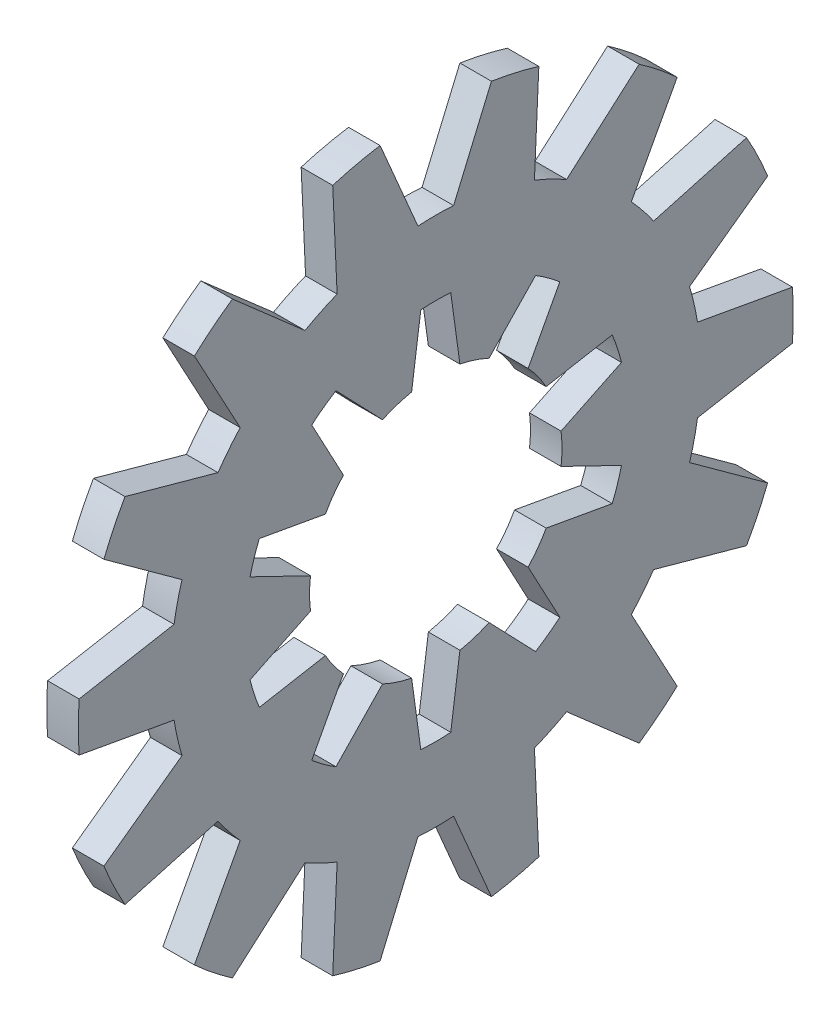
SolidWorks part; units mm, degrees
ref_plane "Plane1" through (0, 0, 0) normal (0, 0, 1) x (1, 0, 0)
ref_plane "Plane2" through (0, 0, 0) normal (0, 1, 0) x (1, 0, 0)
ref_plane "Plane3" through (0, 0, 0) normal (1, 0, 0) x (0, 0, -1)
sketch "SecSke" plane through (0, 0, 0) normal (0, 0, 1) x (1, 0, 0)
  line L0 (-34.925, 0) -> (9.525, 0) construction
  line L1 (0, 3.2512) -> (0, 9.2075)
  line L2 (0, 9.2075) -> (-0.8128, 9.2075)
  line L3 (-0.8128, 9.2075) -> (-0.8128, 3.2512)
  line L4 (-0.8128, 3.2512) -> (0, 3.2512)
  dimension "Thickness" = 0.8128
revolve "Body" add sketch "SecSke" angle 360 about L0
sketch "ExtCutSke" plane through (0, 0, 0) normal (1, 0, 0) x (0, 0, -1)
  line L0 (0, 0) -> (0, 9.6679) construction
  line L1 (-1.6194, 9.5313) -> (-0.4591, 6.8095)
  line L2 (1.6194, 9.5313) -> (0.4591, 6.8095)
  arc A0 (1.6194, 9.5313) -> (-1.6194, 9.5313) centre (0, 0) ccw
  arc A1 (0.4591, 6.8095) -> (-0.4591, 6.8095) centre (0, 0) ccw
extrude "ExtCut" cut sketch "ExtCutSke" against normal through all
pattern_circular "ExtCuts" count 14 every 25.714 about axis through (-34.925, 0, 0) along (1, 0, 0) of "ExtCut"
sketch "IntCutSke" plane through (0, 0, 0) normal (1, 0, 0) x (0, 0, -1)
  line L0 (-0.3859, 4.9038) -> (-0.6453, 3.0205)
  line L1 (0.3859, 4.9038) -> (0.6453, 3.0205)
  line L2 (0, 0) -> (0, 4.919) construction
  arc A0 (0.6453, 3.0205) -> (-0.6453, 3.0205) centre (0, 0) ccw
  arc A1 (0.3859, 4.9038) -> (-0.3859, 4.9038) centre (0, 0) ccw
  dimension "Clr_dia" = 6.1773
  dimension "Clr_ang" = 24.12
  dimension "Cut_ang" = 9
extrude "IntCut" cut sketch "IntCutSke" against normal through all
pattern_circular "IntCuts" count 10 every 36 about axis through (-34.925, 0, 0) along (1, 0, 0) of "IntCut"
equation "' \"Inside_dia@SecSke\" = 16"
equation "' \"Outside_dia@SecSke\" = 35"
equation "' \"Thickness@SecSke\" = 1.4"
equation "' \"Count@ExtCuts\" = 16"
equation "' \"Count@IntCuts\" = 12"
equation "' \"Inside_dia@SecSke\" = 10.5"
equation "' \"Outside_dia@SecSke\" = 26"
equation "' \"Thickness@SecSke\" = 1"
equation "' \"Count@ExtCuts\" = 14"
equation "' \"Count@IntCuts\" = 9"
equation "' \"Inside_dia@SecSke\" = 6.4"
equation "' \"Outside_dia@SecSke\" = 17.5"
equation "' \"Thickness@SecSke\" = 0.8"
equation "' \"Count@ExtCuts\" = 12"
equation "' \"Inside_dia@SecSke\" = 4.3"
equation "' \"Outside_dia@SecSke\" = 15"
equation "' \"Thickness@SecSke\" = 0.6"
equation "' \"Count@IntCuts\" = 8"
equation "\"Angle@ExtCuts\" = 360 / \"Count@ExtCuts\""
equation "\"Clr_dia@ExtCutSke\" =  \"Outside_dia@SecSke\" * 1.05"
equation "\"Cut_dia@ExtCutSke\" = \"Outside_dia@SecSke\" - (\"Outside_dia@SecSke\"  - \"Inside_dia@SecSke\" ) * 0.4"
equation "\"Clr_ang@ExtCutSke\" = (360 / \"Count@ExtCuts\") * 0.75"
equation "\"Cut_ang@ExtCutSke\" = (360 / \"Count@ExtCuts\") * 0.3"
equation "\"Angle@IntCuts\" = 360 / \"Count@IntCuts\""
equation "\"Clr_dia@IntCutSke\" =  \"Inside_dia@SecSke\" * 0.95"
equation "\"cut_dia@IntCutSke\" = \"Inside_dia@SecSke\" +  ( \"Outside_dia@SecSke\" - \"Inside_dia@SecSke\" )  * 0.28"
equation "\"Clr_ang@IntCutSke\" = (360 / \"Count@IntCuts\") * 0.67"
equation "\"Cut_ang@IntCutSke\" = (360 / \"Count@IntCuts\") * 0.25"
